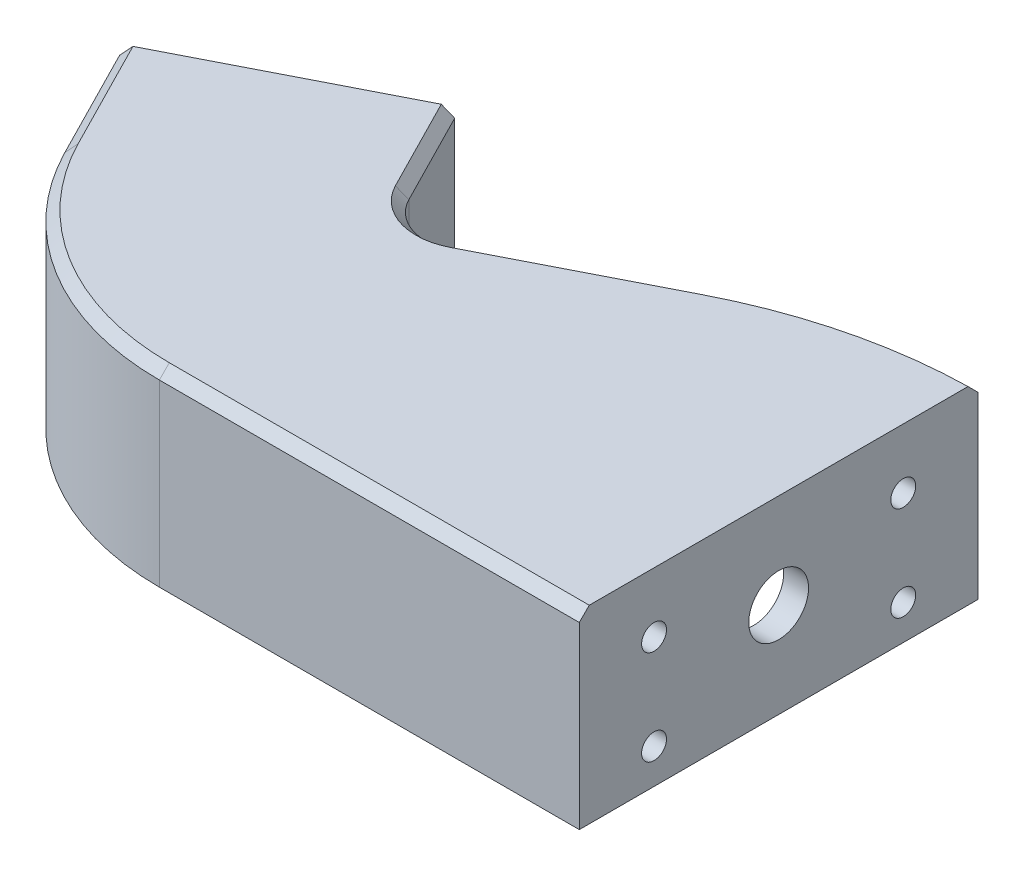
SolidWorks part; units mm, degrees
material "ABS generico"
ref_plane "Piano frontale" through (0, 0, 0) normal (0, 0, 1) x (1, 0, 0)
ref_plane "Piano superiore" through (0, 0, 0) normal (0, 1, 0) x (1, 0, 0)
ref_plane "Piano destro" through (0, 0, 0) normal (1, 0, 0) x (0, 0, -1)
sketch "Schizzo1" plane through (0, 0, 0) normal (0, 1, 0) x (1, 0, 0)
  line L0 (0, -80) -> (0, 0)
  line L1 (0, -80) -> (-84.2581, -80)
  line L2 (0, 0) -> (-22.1057, 0)
  line L4 (-100.1216, -4.8796) -> (-144.6719, -27.5791)
  line L5 (-144.6719, -27.5791) -> (-133.2634, -49.9695)
  line L7 (-100.1216, -4.8796) -> (-90.5557, -23.6537)
  line L8 (-77.1057, -28.0239) -> (-22.1057, 0)
  arc A2 (-84.2581, -80) -> (-133.2634, -49.9695) centre (-84.2581, -25) cw
  arc A3 (-77.1057, -28.0239) -> (-90.5557, -23.6537) centre (-81.6456, -19.1138) cw
  dimension "D6" = 10
  dimension "D7" = 55
  dimension "D1" = 80
  dimension "D2" = 153
  dimension "D3" = 50
  dimension "D4" = 144.6719
  dimension "D5" = 52.4209
  dimension "D8" = 55
extrude "Estrusione-Estrusione1" add sketch "Schizzo1" along normal blind 5
extrude "Estrusione-Sottile1" add sketch "Schizzo1<3>" against normal blind 33 thin thin type one direction reverse wall 5
sketch "Schizzo1<3>" plane through (0, 0, 0) normal (0, 1, 0) x (1, 0, 0) same geometry as "Schizzo1"
fillet "Raccordo1" radius 100 1 edges at (-22.1057, -14, 0)
chamfer "Smusso1" distance 2 angle 45 7 edges at (-138.9677, 5, 38.7743) (-112.9955, 5, 71.8952) (-42.129, 5, 80) (-95.3386, 5, 14.2667) (-84.7358, 5, 28.6244) (-60.2828, 5, 19.4522) (-22.3472, 5, 2.9751)
sketch "Schizzo2" plane through (-18.662, 0, -36.6262) normal (-0.454, 0, -0.891) x (-0.891, 0, 0.454)
  line L0 (104.4243, -13.4918) -> (108.4243, -13.4918) construction
  line L1 (104.4243, -10.9918) -> (108.4243, -10.9918)
  line L2 (104.4243, -15.9918) -> (108.4243, -15.9918)
  line L3 (93.4243, 5) -> (139.4243, 5) construction
  line L5 (124.4243, -13.4918) -> (128.4243, -13.4918) construction
  line L6 (124.4243, -10.9918) -> (128.4243, -10.9918)
  line L7 (124.4243, -15.9918) -> (128.4243, -15.9918)
  line L8 (108.4243, -13.4918) -> (124.4243, -13.4918) construction
  line L11 (141.4243, 3) -> (141.4243, -33) construction
  arc A0 (104.4243, -10.9918) -> (104.4243, -15.9918) centre (104.4243, -13.4918) ccw
  arc A1 (108.4243, -15.9918) -> (108.4243, -10.9918) centre (108.4243, -13.4918) ccw
  arc A2 (124.4243, -10.9918) -> (124.4243, -15.9918) centre (124.4243, -13.4918) ccw
  arc A3 (128.4243, -15.9918) -> (128.4243, -10.9918) centre (128.4243, -13.4918) ccw
  point P2 (106.4243, -13.4918)
  point P13 (126.4243, -13.4918)
  dimension "D1" = 4
  dimension "D2" = 5
  dimension "D3" = 18.4918
  dimension "D4" = 15
  dimension "D5" = 20
extrude "Taglio-Estrusione1" cut sketch "Schizzo2" against normal blind 10
sketch "Schizzo3" plane through (0, 0, 0) normal (1, 0, 0) x (0, 0, -1)
  line L0 (-78, 5) -> (-2.0004, 5) construction
  line L1 (-80, 3) -> (-80, -33) construction
  line L3 (-65, -7) -> (-15, -7) construction
  line L4 (-65, -7) -> (-65, -26) construction
  line L5 (-65, -26) -> (-15, -26) construction
  line L6 (-15, -7) -> (-15, -26) construction
  line L7 (-80, -33) -> (0, -33) construction
  circle A0 centre (-65, -7) radius 2.5
  circle A2 centre (-15, -7) radius 2.5
  circle A3 centre (-15, -26) radius 2.5
  circle A4 centre (-65, -26) radius 2.5
  circle A5 centre (-40, -14) radius 6
  dimension "D5" = 5
  dimension "D8" = 12
  dimension "D1" = 12
  dimension "D2" = 15
  dimension "D3" = 19
  dimension "D4" = 50
  dimension "D6" = 19
  dimension "D7" = 40
extrude "Taglio-Estrusione2" cut sketch "Schizzo3" against normal blind 10 contours A4 | A0 | A2 | A3 region at (0, -7, 65) region at (0, -7, 15) region at (0, -26, 15) region at (0, -26, 65)
extrude "Taglio-Estrusione3" cut sketch "Schizzo3<4>" against normal blind 161 contours A5 region at (0, -14, 40)
sketch "Schizzo3<4>" plane through (0, 0, 0) normal (1, 0, 0) x (0, 0, -1) same geometry as "Schizzo3"
